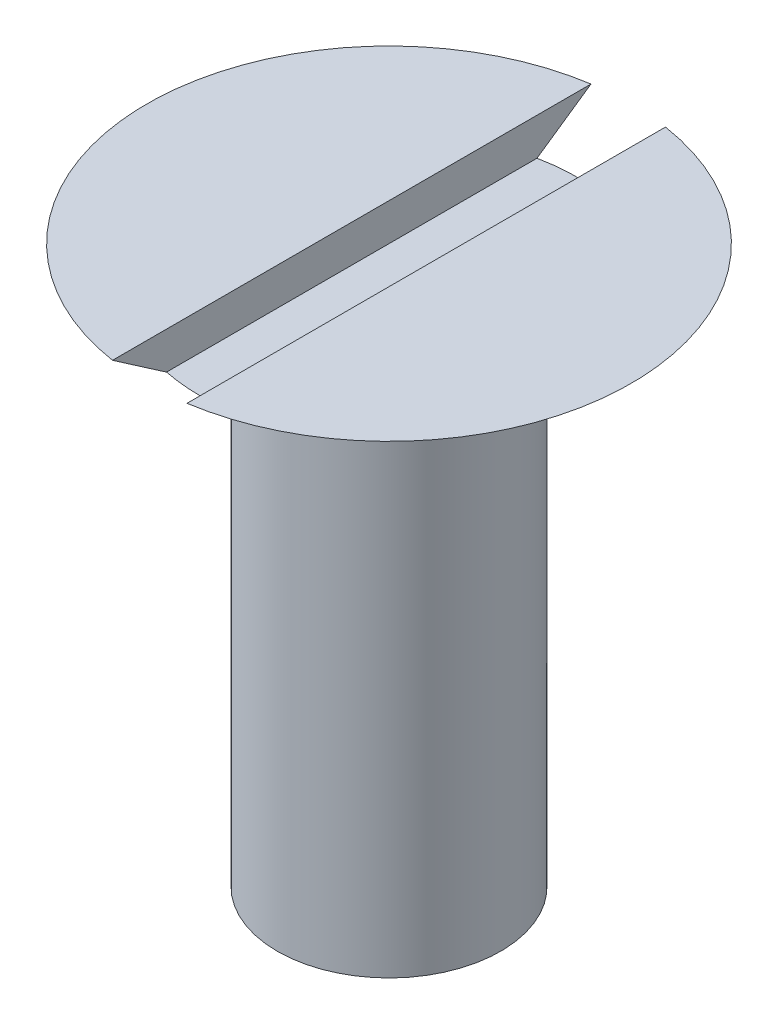
SolidWorks part; units mm, degrees
ref_plane "Front Plane" through (0, 0, 0) normal (0, 0, 1) x (1, 0, 0)
ref_plane "Top Plane" through (0, 0, 0) normal (0, 1, 0) x (1, 0, 0)
ref_plane "Right Plane" through (0, 0, 0) normal (1, 0, 0) x (0, 0, -1)
sketch "Sketch1" plane through (0, 0, 0) normal (0, 0, 1) x (1, 0, 0)
  line L0 (3, 12.5) -> (6.5, 14.9507)
  line L1 (0, 0) -> (3, 0)
  line L2 (0, 0) -> (0, 12.5)
  line L3 (0, 12.5) -> (3, 12.5)
  line L4 (3, 0) -> (3, 12.5)
  line L5 (6.5, 14.9507) -> (0, 14.9507)
  line L6 (0, 14.9507) -> (0, 12.5)
  line L7 (0, 14.9507) -> (0, 12.5)
  line L8 (1, 14.9507) -> (1, 13.9507)
  line L9 (1, 13.9507) -> (-1, 13.9507)
  line L10 (3, 0) -> (0, -1.7321)
  line L11 (0, -1.7321) -> (0, 0)
  line L12 (0, 0) -> (3, 0) construction
  line L13 (0, 14.9507) -> (0, 12.5)
  line L14 (0, 0) -> (0, -1.7321)
  line L15 (-1, 14.9507) -> (-1, 13.9507)
  line L16 (-1, 14.9507) -> (0, 14.9507)
  point P16 (0, 13.9507)
  dimension "D1" = 12.5
  dimension "D2" = 3
  dimension "D3" = 6.5
  dimension "D4" = 145
  dimension "D5" = 1
  dimension "D6" = 1
  dimension "D7" = 60
revolve "Revolve1" add sketch "Sketch1" angle 360 about L6 region at (2.6688, 13.8218, 0) region at (1.5, 6.25, 0) region at (1, -0.5774, 0) region at (0.5, 14.4507, 0)
extrude "Cut-Extrude1" cut sketch "Sketch1<4>" against normal through all both and the other way through all contours L16 L15 L9 L6 | L9 L8 L5 L6 region at (0.5, 14.4507, 0) region at (-0.5, 14.4507, 0)
sketch "Sketch1<4>" plane through (0, 0, 0) normal (0, 0, 1) x (1, 0, 0) same geometry as "Sketch1"
